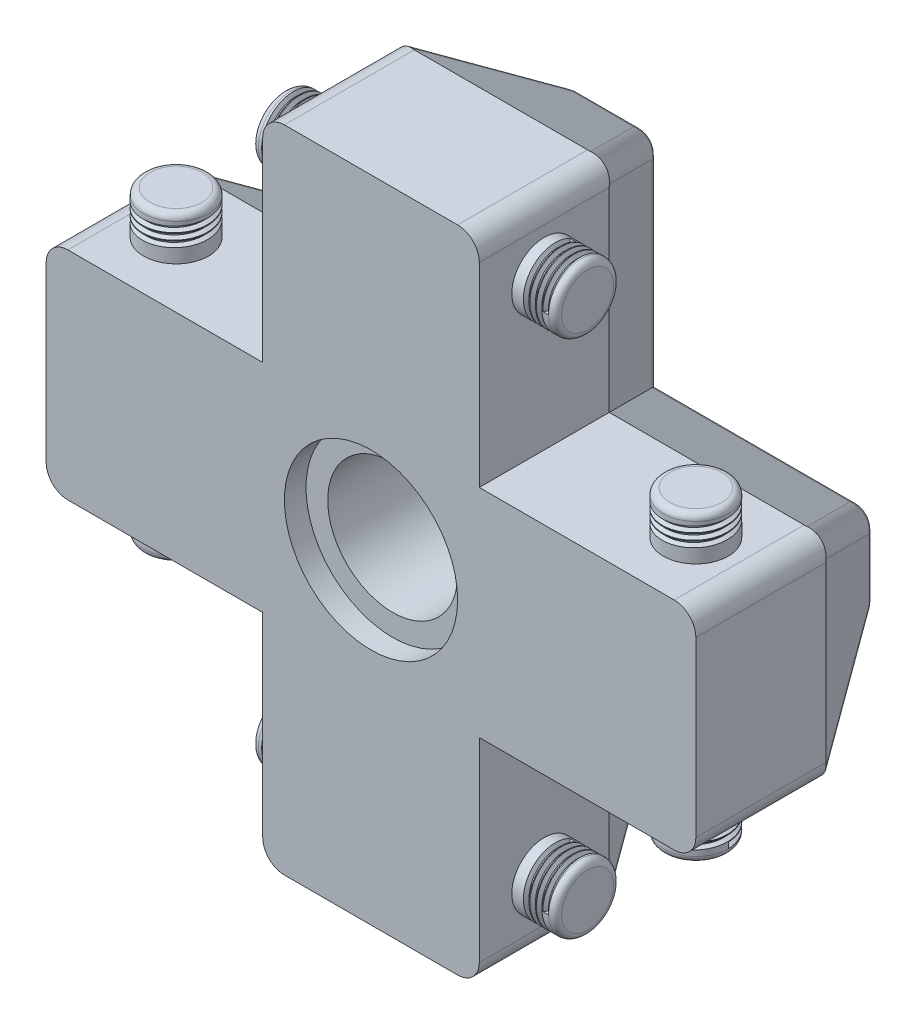
SolidWorks part; units mm, degrees
ref_plane "Front Plane" through (0, 0, 0) normal (0, 0, 1) x (1, 0, 0)
ref_plane "Top Plane" through (0, 0, 0) normal (0, 1, 0) x (1, 0, 0)
ref_plane "Right Plane" through (0, 0, 0) normal (1, 0, 0) x (0, 0, -1)
sketch "Esquisse1" plane through (0, 0, 0) normal (0, 0, 1) x (1, 0, 0)
  circle A0 centre (0, 0) radius 14
  dimension "D1" = 28
extrude "Boss.-Extru.1" add sketch "Esquisse1" along normal blind 76
sketch "Esquisse2" plane through (0, 0, 76) normal (0, 0, 1) x (1, 0, 0)
  line L1 (-75, -25) -> (75, -25)
  line L2 (-75, -25) -> (-75, 25)
  line L3 (-75, 25) -> (75, 25)
  line L4 (75, -25) -> (75, 25)
  line L5 (-75, -25) -> (75, 25) construction
  line L6 (-75, 25) -> (75, -25) construction
  line L7 (-25, -75) -> (25, -75)
  line L8 (-25, -75) -> (-25, 75)
  line L9 (-25, 75) -> (25, 75)
  line L10 (25, -75) -> (25, 75)
  line L11 (-25, -75) -> (25, 75) construction
  line L12 (-25, 75) -> (25, -75) construction
  point P0 (0, 0)
  point P6 (0, 0)
  circle M5 centre (0, 0) radius 14
  dimension "D1" = 150
  dimension "D2" = 150
  dimension "D3" = 50
  dimension "D4" = 50
extrude "Boss.-Extru.2" add sketch "Esquisse2" along normal blind 30 contours L3 L10 L9 L8 | L10 L1 L4 L3 | L7 L10 L1 L8 | L1 L8 L3 L2 | L1 L10 L3 L8 M5 | M5 region at (-50, 0, 76) region at (-24.2929, 0, 76) region at (0, -50, 76) region at (50, 0, 76) region at (0, 50, 76) region at (0, 0, 76)
ref_plane "Plan2" through (0, 0, 0) normal (-1, 0, 0) x (0, 0, 1)
sketch "Esquisse3" plane through (0, 0, 0) normal (-1, 0, 0) x (0, 0, 1)
  line L0 (91, 75) -> (91, 25) construction
  line L1 (106, 75) -> (76, 75) construction
  line L2 (106, 25) -> (76, 25) construction
  line L3 (0, 0) -> (76, 0) construction
  line L4 (76, -25) -> (76, 25) construction
  circle A0 centre (91, 60) radius 7.5
  circle A1 centre (91, -60) radius 7.5
  dimension "D2" = 15
  dimension "D1" = 15
extrude "Boss.-Extru.3" add sketch "Esquisse3" along normal mid plane 70
sketch "Esquisse4" plane through (0, 0, 0) normal (0, 1, 0) x (1, 0, 0)
  line L0 (-75, -91) -> (-25, -91) construction
  line L1 (-75, -106) -> (-75, -76) construction
  line L2 (-25, -83.5) -> (-25, -98.5) construction
  line L3 (0, 0) -> (0, -76) construction
  line L4 (-25, -76) -> (25, -76) construction
  circle A0 centre (-60, -91) radius 7.5
  circle A1 centre (60, -91) radius 7.5
  dimension "D1" = 15
  dimension "D2" = 15
extrude "Boss.-Extru.4" add sketch "Esquisse4" along normal mid plane 70
sketch "Esquisse5" plane through (0, 0, 76) normal (0, 0, -1) x (-1, 0, 0)
  line L12 (25, 25) -> (25, 75)
  line L13 (25, 75) -> (-25, 75)
  line L14 (-25, 75) -> (-25, 25)
  line L15 (-25, 25) -> (-75, 25)
  line L16 (-75, 25) -> (-75, -25)
  line L17 (-75, -25) -> (-25, -25)
  line L18 (-25, -25) -> (-25, -75)
  line L19 (-25, -75) -> (25, -75)
  line L20 (25, -75) -> (25, -25)
  line L21 (25, -25) -> (75, -25)
  line L22 (75, -25) -> (75, 25)
  line L23 (75, 25) -> (25, 25)
  line L24 (25, 25) -> (25, 75)
  line L25 (25, 75) -> (-25, 75)
  line L26 (-25, 75) -> (-25, 25)
  line L27 (-25, 25) -> (-75, 25)
  line L28 (-75, 25) -> (-75, -25)
  line L29 (-75, -25) -> (-25, -25)
  line L30 (-25, -25) -> (-25, -75)
  line L31 (-25, -75) -> (25, -75)
  line L32 (25, -75) -> (25, -25)
  line L33 (25, -25) -> (75, -25)
  line L34 (75, -25) -> (75, 25)
  line L35 (75, 25) -> (25, 25)
  dimension "D1" = 0
extrude "Boss.-Extru.5" add sketch "Esquisse5" along normal blind 26 draft 30
fillet "Congé1" radius 5 28 edges at (75, -25, 91) (75, 25, 91) (67.4944, 17.4944, 63) (67.4944, -17.4944, 63) (25, 75, 91) (-25, 75, 91) (-17.4944, 67.4944, 63) (17.4944, 67.4944, 63) (-75, 25, 91) (-75, -25, 91) (-25, -75, 91) (25, -75, 91) (17.4944, -67.4944, 63) (-17.4944, -67.4944, 63) (-67.4944, -17.4944, 63) (-67.4944, 17.4944, 63) (-59.9889, 0, 50) (-34.9889, -9.9889, 50) (-9.9889, -34.9889, 50) (0, -59.9889, 50) (9.9889, -34.9889, 50) (34.9889, -9.9889, 50) (59.9889, 0, 50) (34.9889, 9.9889, 50) (9.9889, 34.9889, 50) (0, 59.9889, 50) (-9.9889, 34.9889, 50) (-34.9889, 9.9889, 50)
fillet "Congé2" radius 1.5 8 edges at (60, -35, 83.5) (-60, 35, 98.5) (35, -60, 83.5) (-60, -35, 98.5) (-35, -60, 83.5) (-35, 60, 98.5) (60, 35, 83.5) (35, 60, 98.5)
thread "Filetage1" pitch 1.5 method cut profile "Profil de filetage1" start angle 0, offset 0, length 5, pitch 1.5, diameter 15
ref_plane "Plan3" through (-52.5, -33.5, 91) normal (0, 0, 1) x (1, 0, 0)
sketch "Profil de filetage1" plane through (-52.5, -33.5, 91) normal (0, 0, 1) x (1, 0, 0)
  line L0 (0, 0) -> (0, 1.5) construction
  line L11 (0, 0) -> (0, 1.3125)
  line L12 (0, 1.3125) -> (-0.8119, 0.8437)
  line L13 (-0.8119, 0.8437) -> (-0.8119, 0.4687)
  line L15 (-0.8119, 0.4687) -> (0, 0)
  line L17 (-0.8119, 0.6562) -> (0, 0.6562) construction
  point P2 (0, 0)
  dimension "Pitch" = 1.5
  dimension "Profile_Angle" = 60
  dimension "Profile_Land" = 0.375
  dimension "Profile_Height" = 0.8119
thread "Filetage2" pitch 1.5 method cut profile "Profil de filetage2" start angle 0, offset 0, length 5, pitch 1.5, diameter 15
ref_plane "Plan4" through (-67.5, 33.5, 91) normal (0, 0, 1) x (-1, 0, 0)
sketch "Profil de filetage2" plane through (-67.5, 33.5, 91) normal (0, 0, 1) x (-1, 0, 0)
  line L0 (0, 0) -> (0, 1.5) construction
  line L11 (0, 0) -> (0, 1.3125)
  line L12 (0, 1.3125) -> (-0.8119, 0.8437)
  line L13 (-0.8119, 0.8437) -> (-0.8119, 0.4687)
  line L15 (-0.8119, 0.4687) -> (0, 0)
  line L17 (-0.8119, 0.6562) -> (0, 0.6562) construction
  point P2 (0, 0)
  dimension "Pitch" = 1.5
  dimension "Profile_Angle" = 60
  dimension "Profile_Land" = 0.375
  dimension "Profile_Height" = 0.8119
thread "Filetage3" pitch 1.5 method cut profile "Profil de filetage3" start angle 0, offset 0, length 5, pitch 1.5, diameter 15
ref_plane "Plan5" through (-33.5, 60, 83.5) normal (0, -1, 0) x (0, 0, -1)
sketch "Profil de filetage3" plane through (-33.5, 60, 83.5) normal (0, -1, 0) x (0, 0, -1)
  line L0 (0, 0) -> (0, 1.5) construction
  line L11 (0, 0) -> (0, 1.3125)
  line L12 (0, 1.3125) -> (-0.8119, 0.8437)
  line L13 (-0.8119, 0.8437) -> (-0.8119, 0.4687)
  line L15 (-0.8119, 0.4687) -> (0, 0)
  line L17 (-0.8119, 0.6562) -> (0, 0.6562) construction
  point P2 (0, 0)
  dimension "Pitch" = 1.5
  dimension "Profile_Angle" = 60
  dimension "Profile_Land" = 0.375
  dimension "Profile_Height" = 0.8119
thread "Filetage4" pitch 1.5 method cut profile "Profil de filetage4" start angle 0, offset 0, length 5, pitch 1.5, diameter 15
ref_plane "Plan6" through (33.5, 60, 98.5) normal (0, -1, 0) x (0, 0, 1)
sketch "Profil de filetage4" plane through (33.5, 60, 98.5) normal (0, -1, 0) x (0, 0, 1)
  line L0 (0, 0) -> (0, 1.5) construction
  line L11 (0, 0) -> (0, 1.3125)
  line L12 (0, 1.3125) -> (-0.8119, 0.8437)
  line L13 (-0.8119, 0.8437) -> (-0.8119, 0.4687)
  line L15 (-0.8119, 0.4687) -> (0, 0)
  line L17 (-0.8119, 0.6562) -> (0, 0.6562) construction
  point P2 (0, 0)
  dimension "Pitch" = 1.5
  dimension "Profile_Angle" = 60
  dimension "Profile_Land" = 0.375
  dimension "Profile_Height" = 0.8119
thread "Filetage5" pitch 1.5 method cut profile "Profil de filetage5" start angle 0, offset 0, length 5, pitch 1.5, diameter 15
ref_plane "Plan7" through (52.5, 33.5, 91) normal (0, 0, 1) x (-1, 0, 0)
sketch "Profil de filetage5" plane through (52.5, 33.5, 91) normal (0, 0, 1) x (-1, 0, 0)
  line L0 (0, 0) -> (0, 1.5) construction
  line L11 (0, 0) -> (0, 1.3125)
  line L12 (0, 1.3125) -> (-0.8119, 0.8437)
  line L13 (-0.8119, 0.8437) -> (-0.8119, 0.4687)
  line L15 (-0.8119, 0.4687) -> (0, 0)
  line L17 (-0.8119, 0.6562) -> (0, 0.6562) construction
  point P2 (0, 0)
  dimension "Pitch" = 1.5
  dimension "Profile_Angle" = 60
  dimension "Profile_Land" = 0.375
  dimension "Profile_Height" = 0.8119
thread "Filetage6" pitch 1.5 method cut profile "Profil de filetage6" start angle 0, offset 0, length 5, pitch 1.5, diameter 15
ref_plane "Plan8" through (67.5, -33.5, 91) normal (0, 0, 1) x (1, 0, 0)
sketch "Profil de filetage6" plane through (67.5, -33.5, 91) normal (0, 0, 1) x (1, 0, 0)
  line L0 (0, 0) -> (0, 1.5) construction
  line L11 (0, 0) -> (0, 1.3125)
  line L12 (0, 1.3125) -> (-0.8119, 0.8437)
  line L13 (-0.8119, 0.8437) -> (-0.8119, 0.4687)
  line L15 (-0.8119, 0.4687) -> (0, 0)
  line L17 (-0.8119, 0.6562) -> (0, 0.6562) construction
  point P2 (0, 0)
  dimension "Pitch" = 1.5
  dimension "Profile_Angle" = 60
  dimension "Profile_Land" = 0.375
  dimension "Profile_Height" = 0.8119
thread "Filetage7" pitch 1.5 method cut profile "Profil de filetage7" start angle 0, offset 0, length 5, pitch 1.5, diameter 15
ref_plane "Plan9" through (33.5, -60, 98.5) normal (0, -1, 0) x (0, 0, 1)
sketch "Profil de filetage7" plane through (33.5, -60, 98.5) normal (0, -1, 0) x (0, 0, 1)
  line L0 (0, 0) -> (0, 1.5) construction
  line L11 (0, 0) -> (0, 1.3125)
  line L12 (0, 1.3125) -> (-0.8119, 0.8437)
  line L13 (-0.8119, 0.8437) -> (-0.8119, 0.4687)
  line L15 (-0.8119, 0.4687) -> (0, 0)
  line L17 (-0.8119, 0.6562) -> (0, 0.6562) construction
  point P2 (0, 0)
  dimension "Pitch" = 1.5
  dimension "Profile_Angle" = 60
  dimension "Profile_Land" = 0.375
  dimension "Profile_Height" = 0.8119
thread "Filetage8" pitch 1.5 method cut profile "Profil de filetage8" start angle 0, offset 0, length 5, pitch 1.5, diameter 15
ref_plane "Plan10" through (-33.5, -60, 83.5) normal (0, -1, 0) x (0, 0, -1)
sketch "Profil de filetage8" plane through (-33.5, -60, 83.5) normal (0, -1, 0) x (0, 0, -1)
  line L0 (0, 0) -> (0, 1.5) construction
  line L11 (0, 0) -> (0, 1.3125)
  line L12 (0, 1.3125) -> (-0.8119, 0.8437)
  line L13 (-0.8119, 0.8437) -> (-0.8119, 0.4687)
  line L15 (-0.8119, 0.4687) -> (0, 0)
  line L17 (-0.8119, 0.6562) -> (0, 0.6562) construction
  point P2 (0, 0)
  dimension "Pitch" = 1.5
  dimension "Profile_Angle" = 60
  dimension "Profile_Land" = 0.375
  dimension "Profile_Height" = 0.8119
sketch "Esquisse22" plane through (0, 0, 106) normal (0, 0, 1) x (1, 0, 0)
  circle A0 centre (0, 0) radius 15
  dimension "D1" = 30
extrude "Enlèv. mat.-Extru.1" cut sketch "Esquisse22" against normal through all
sketch "Esquisse23" plane through (0, 0, 106) normal (0, 0, 1) x (1, 0, 0)
  circle A0 centre (0, 0) radius 20
  dimension "D1" = 40
extrude "Enlèv. mat.-Extru.2" cut sketch "Esquisse23" against normal blind 5
